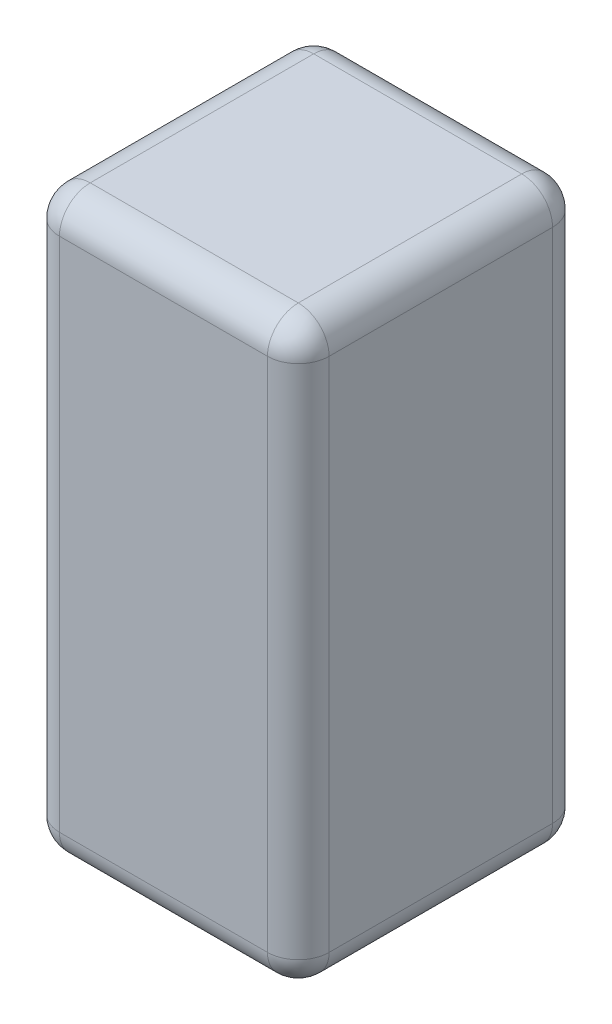
SolidWorks part; units mm, degrees
ref_plane "Front Plane" through (0, 0, 0) normal (0, 0, 1) x (1, 0, 0)
ref_plane "Top Plane" through (0, 0, 0) normal (0, 1, 0) x (1, 0, 0)
ref_plane "Right Plane" through (0, 0, 0) normal (1, 0, 0) x (0, 0, -1)
sketch "Sketch2" plane through (0, 0, 4) normal (0, 0, 1) x (1, 0, 0)
  line L0 (0, 0) -> (28.6597, 0) construction
  line L1 (17.5, 37.5) -> (-17.5, 37.5)
  line L2 (17.5, 37.5) -> (17.5, -37.5)
  line L3 (17.5, -37.5) -> (-17.5, -37.5)
  line L4 (-17.5, 37.5) -> (-17.5, -37.5)
  line L5 (0, 0) -> (0, 59.8919) construction
  point P7 (0, 0)
  point P9 (0, 0)
  dimension "D1" = 35
  dimension "D2" = 75
  dimension "D3" = 17.5
  dimension "D4" = 37.5
extrude "Boss-Extrude1" add sketch "Sketch2" along normal blind 37
fillet "Fillet1" radius 4 12 edges at (17.5, 0, 4) (17.5, 0, 41) (0, -37.5, 41) (0, -37.5, 4) (-17.5, 0, 4) (-17.5, 0, 41) (0, 37.5, 41) (0, 37.5, 4) (17.5, 37.5, 22.5) (-17.5, 37.5, 22.5) (17.5, -37.5, 22.5) (-17.5, -37.5, 22.5)
